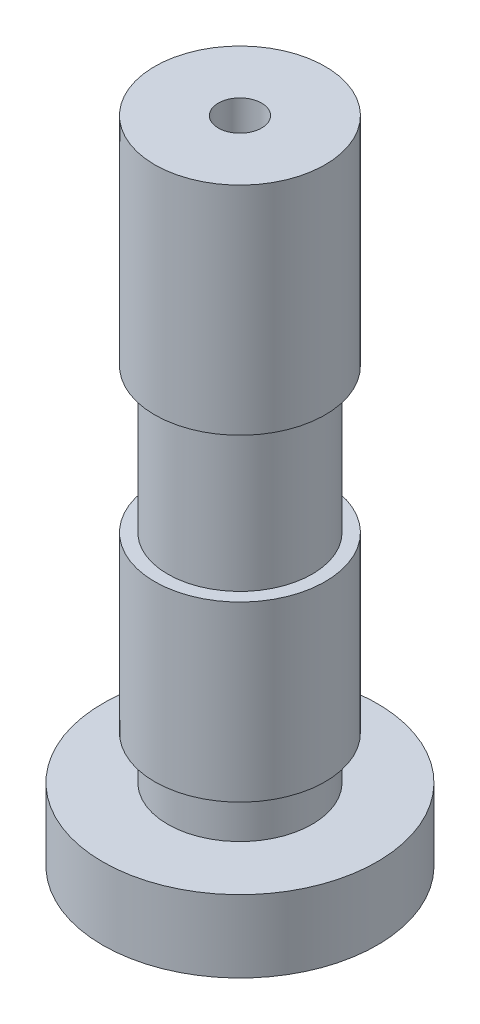
SolidWorks part; units mm, degrees
ref_plane "Спереди" through (0, 0, 0) normal (0, 0, 1) x (1, 0, 0)
ref_plane "Сверху" through (0, 0, 0) normal (0, 1, 0) x (1, 0, 0)
ref_plane "Справа" through (0, 0, 0) normal (1, 0, 0) x (0, 0, -1)
sketch "Эскиз1" plane through (0, 0, 0) normal (0, 0, 1) x (1, 0, 0)
  line L0 (0, 14.6468) -> (0, -10.5782) construction
  line L1 (0, 0) -> (9.5, 0)
  line L2 (9.5, 0) -> (9.5, 5)
  line L3 (9.5, 5) -> (5, 5)
  line L4 (5, 5) -> (5, 8)
  line L5 (5, 8) -> (5.9, 8)
  line L6 (5.9, 8) -> (5.9, 20)
  line L7 (5.9, 20) -> (5, 20)
  line L9 (5.9, 45) -> (0, 45)
  line L10 (0, 45) -> (0, 0)
  line L11 (5, 20) -> (5, 30)
  line L12 (5, 30) -> (5.9, 30)
  line L13 (5.9, 30) -> (5.9, 45)
  line L14 (5, 25) -> (-6.4103, 25) construction
  dimension "D1" = 19
  dimension "D2" = 5
  dimension "D3" = 3
  dimension "D4" = 45
  dimension "D5" = 15
  dimension "D6" = 12
  dimension "D7" = 11.8
  dimension "D8" = 10
revolve "Повернуть1" add sketch "Эскиз1" angle 360 about L0
sketch "Эскиз2" plane through (0, 45, 0) normal (0, 1, 0) x (1, 0, 0)
  circle A0 centre (0, 0) radius 1.5
  dimension "D1" = 3
extrude "Вырез-Вытянуть1" cut sketch "Эскиз2" against normal blind 3
sketch "Эскиз3" plane through (0, 0, 0) normal (0, -1, 0) x (-1, 0, 0)
  circle A0 centre (0, 0) radius 1.5
  dimension "D1" = 3
extrude "Вырез-Вытянуть2" cut sketch "Эскиз3" against normal blind 3
